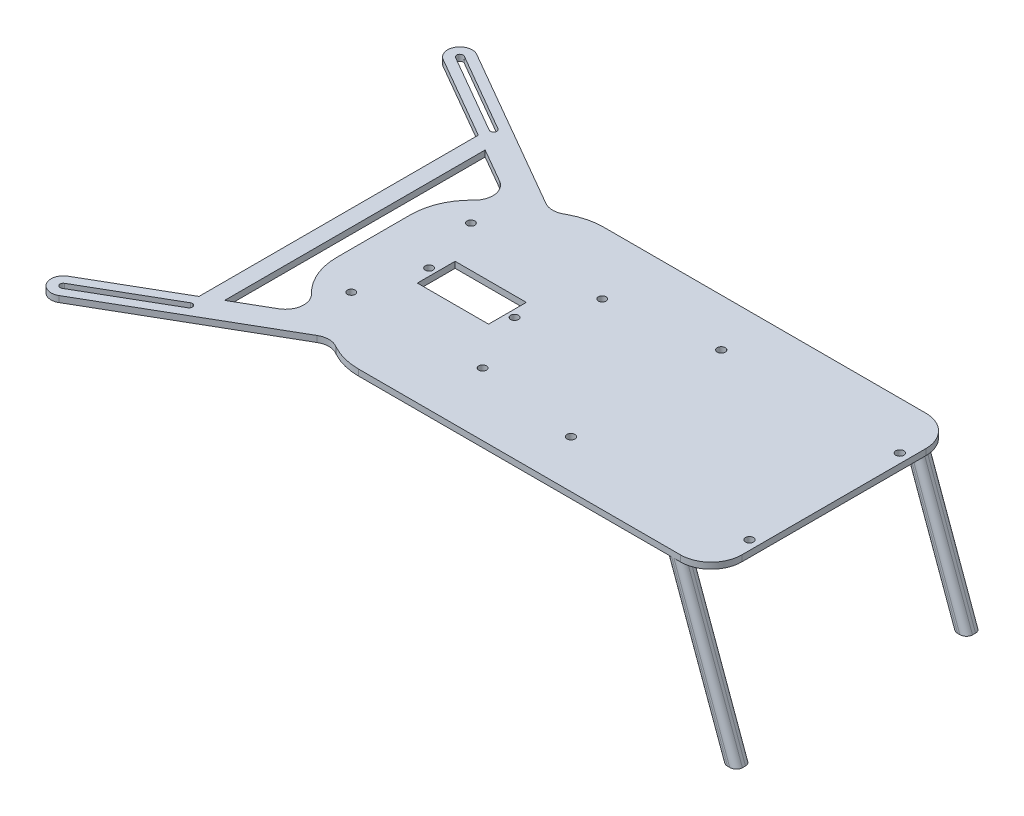
SolidWorks part; units mm, degrees
ref_plane "前视基准面" through (0, 0, 0) normal (0, 0, 1) x (1, 0, 0)
ref_plane "上视基准面" through (0, 0, 0) normal (0, 1, 0) x (1, 0, 0)
ref_plane "右视基准面" through (0, 0, 0) normal (1, 0, 0) x (0, 0, -1)
other "Configuration Table"
sketch "草图1" plane through (0, 0, 0) normal (0, 1, 0) x (1, 0, 0)
  line L0 (-41.4, 52.9432) -> (-41.4, -59.5525) construction
  line L1 (-75, -40) -> (75, -40)
  line L2 (-75, -40) -> (-75, 40)
  line L3 (-75, 40) -> (75, 40)
  line L4 (75, -40) -> (75, 40)
  line L5 (-75, -40) -> (75, 40) construction
  line L6 (-75, 40) -> (75, -40) construction
  line L7 (-75, 0) -> (32.4957, 0) construction
  circle A0 centre (-62.8, 19.5) radius 1.25
  circle A1 centre (-20, 19.5) radius 1.25
  circle A2 centre (-20, -19.5) radius 1.25
  circle A3 centre (-62.8, -19.5) radius 1.25
  point P0 (0, 0)
  dimension "D3" = 42.8
  dimension "D5" = 2.5
  dimension "D1" = 80
  dimension "D2" = 150
  dimension "D4" = 39
  dimension "D6" = 42.8
  dimension "D7" = 95
extrude "凸台-拉伸1" add sketch "草图1" along normal blind 2
sketch "草图2" plane through (0, 2, 0) normal (0, 1, 0) x (1, 0, 0)
  line L0 (-75, 0) -> (82.1354, 0) construction
  line L2 (42.9, 0) -> (42.9, 53.5496) construction
  line L3 (75, -40) -> (75, 40) construction
  circle A0 centre (13.8, 24.5) radius 1.3
  circle A1 centre (72, 24.5) radius 1.3
  circle A2 centre (13.8, -24.5) radius 1.3
  circle A3 centre (72, -24.5) radius 1.3
  dimension "D2" = 2.6
  dimension "D1" = 58.2
  dimension "D3" = 49
  dimension "D4" = 58.2
  dimension "D5" = 3
extrude "切除-拉伸1" cut sketch "草图2" against normal blind 2
sketch "草图3" plane through (0, 2, 0) normal (0, 1, 0) x (1, 0, 0)
  line L0 (0, 0) -> (90.8282, 0) construction
  line L1 (-75, 40) -> (-45, 40)
  line L2 (75, 40) -> (-75, 40) construction
  line L3 (-45, 40) -> (-75, 24)
  line L4 (-75, 40) -> (-75, -40) construction
  line L5 (-75, 24) -> (-75, 40)
  line L6 (-45, -40) -> (-75, -24)
  line L7 (-75, -40) -> (-45, -40)
  line L8 (-75, -24) -> (-75, -40)
  dimension "D1" = 30
  dimension "D2" = 16
extrude "切除-拉伸2" cut sketch "草图3" against normal blind 2
fillet "圆角1" radius 20 4 edges at (-45, 1, -40) (-75, 1, -24) (-45, 1, 40) (-75, 1, 24)
fillet "圆角2" radius 10 2 edges at (75, 1, -40) (75, 1, 40)
sketch "草图4" plane through (0, 2, 0) normal (0, 1, 0) x (1, 0, 0)
  line L0 (-75, 0) -> (35.4397, 0) construction
  line L2 (-75, 12) -> (-75, -12) construction
  line L3 (-54.6, -6.15) -> (-31.4, -6.15)
  line L4 (-54.6, -6.15) -> (-54.6, 6.15)
  line L5 (-54.6, 6.15) -> (-31.4, 6.15)
  line L6 (-31.4, -6.15) -> (-31.4, 6.15)
  line L7 (-54.6, -6.15) -> (-31.4, 6.15) construction
  line L8 (-54.6, 6.15) -> (-31.4, -6.15) construction
  line L9 (-43, 0) -> (-43, -46.9743) construction
  circle A0 centre (-29.075, 0) radius 1.25
  circle A1 centre (-56.925, 0) radius 1.25
  point P1 (-43, 0)
  dimension "D5" = 2.5
  dimension "D1" = 23.2
  dimension "D2" = 12.3
  dimension "D3" = 32
  dimension "D4" = 46.9743
  dimension "D6" = 27.85
extrude "切除-拉伸3" cut sketch "草图4" against normal up to next
sketch "草图5" plane through (0, 0, 40) normal (0, 0, 1) x (1, 0, 0)
  line L0 (65, 0) -> (83.1985, -50)
  line L1 (83.1985, -50) -> (78.1985, -50)
  line L2 (78.1985, -50) -> (60, 0)
  line L3 (60, 0) -> (65, 0)
  line L4 (-40, 0) -> (65, 0) construction
  dimension "D1" = 5
  dimension "D2" = 110
  dimension "D3" = 50
extrude "凸台-拉伸2" add sketch "草图5" against normal blind 5
mirror "镜向1" about plane through (0, 0, 0) normal (0, 0, 1) of "凸台-拉伸2"
fillet "圆角5" radius 2 8 edges at (69.0993, -25, 40) (74.0993, -25, 40) (69.0993, -25, 35) (74.0993, -25, 35) (74.0993, -25, -40) (74.0993, -25, -35) (69.0993, -25, -35) (69.0993, -25, -40)
sketch "草图6" plane through (0, 2, 0) normal (0, 1, 0) x (1, 0, 0)
  line L0 (-53.2423, 35.6041) -> (-61.5593, 31.1684)
  line L1 (-64.4118, 29.6471) -> (-49.4118, 37.6471) construction
  line L2 (-61.5593, 31.1684) -> (-113.5209, 61.1684)
  line L4 (-109.5209, 68.0966) -> (-53.2423, 35.6041)
  line L5 (-61.5593, 31.1684) -> (-111.5593, 31.1684) construction
  line L6 (-61.5593, 31.1684) -> (-48.2765, 54.1749) construction
  line L7 (-111.5209, 64.6325) -> (-85.5401, 49.6325) construction
  line L8 (-110.9959, 65.5418) -> (-85.0151, 50.5418)
  line L9 (-112.0459, 63.7231) -> (-86.0651, 48.7231)
  arc A0 (-109.5209, 68.0966) -> (-113.5209, 61.1684) centre (-111.5209, 64.6325) ccw
  arc A1 (-110.9959, 65.5418) -> (-112.0459, 63.7231) centre (-111.5209, 64.6325) ccw
  arc A2 (-86.0651, 48.7231) -> (-85.0151, 50.5418) centre (-85.5401, 49.6325) ccw
  point P7 (-98.5305, 57.1325)
  dimension "D1" = 30
  dimension "D4" = 1.05
  dimension "D2" = 8
  dimension "D3" = 60
  dimension "D5" = 30
extrude "凸台-拉伸3" add sketch "草图6" against normal blind 2
mirror "镜向2" about plane through (0, 0, 0) normal (0, 0, 1) of "凸台-拉伸3"
fillet "圆角6" radius 6 4 edges at (-53.2423, 1, 35.6041) (-61.5593, 1, 31.1684) (-53.2423, 1, -35.6041) (-61.5593, 1, -31.1684)
sketch "草图7" plane through (0, 0, 0) normal (0, 0, 1) x (1, 0, 0)
  line L0 (-56.1269, 2) -> (-109.5209, 2) construction
  line L1 (-86.4232, 2) -> (-81.1269, 2)
  line L2 (-86.4232, 2) -> (-86.4232, 0)
  line L3 (-86.4232, 0) -> (-81.1269, 0)
  line L4 (-81.1269, 2) -> (-81.1269, 0)
  line L5 (-56.1269, 0) -> (-109.5209, 0) construction
  line L6 (-56.1269, 0) -> (-56.1269, 2) construction
  point P10 (0, 0)
  dimension "D1" = 25
  dimension "D2" = 5.2964
extrude "凸台-拉伸4" add sketch "草图7" against normal up to next and the other way up to next contours L3 L4 L1 L2
